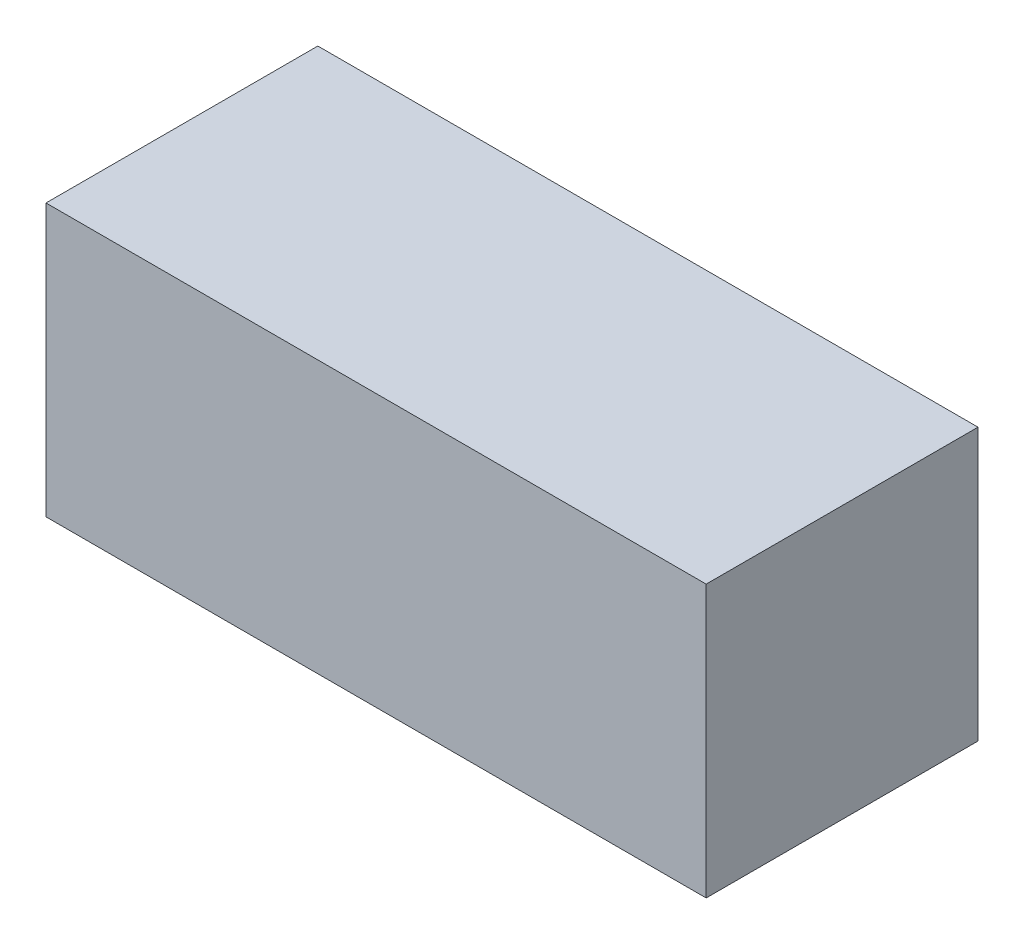
SolidWorks part; units mm, degrees
ref_plane "Front Plane"
ref_plane "Top Plane" through (0, 0, 0) normal (0, 1, 0) x (1, 0, 0)
ref_plane "Right Plane" through (0, 0, 0) normal (1, 0, 0) x (0, 0, -1)
sketch "Sketch1" plane through (0, 0, 0) normal (0, 1, 0) x (1, 0, 0)
  line L1 (-85, -35) -> (85, -35)
  line L2 (-85, -35) -> (-85, 35)
  line L3 (-85, 35) -> (85, 35)
  line L4 (85, -35) -> (85, 35)
  line L5 (-85, -35) -> (85, 35) construction
  line L6 (-85, 35) -> (85, -35) construction
  point P0 (0, 0)
  dimension "D1" = 170
  dimension "D2" = 70
extrude "Boss-Extrude1" add sketch "Sketch1" along normal blind 70
sketch "Sketch2" plane through (-85, 0, 0) normal (-1, 0, 0) x (0, 0, 1)
  line L0 (0, 0) -> (0, 70) construction
  line L4 (-35, 0) -> (35, 0)
  line L5 (35, 0) -> (35, 70)
  line L6 (35, 70) -> (-35, 70)
  line L7 (-35, 70) -> (-35, 0)
  line L8 (-35, 0) -> (35, 0) construction
  line L9 (35, 0) -> (35, 70) construction
  line L10 (35, 70) -> (-35, 70) construction
  line L11 (-35, 70) -> (-35, 0) construction
  point P6 (0, 35)
  point P7 (0, 0)
  point P8 (0, 17.4859)
  point P9 (0, 0)
  dimension "D1" = 0
ref_axis "Axis1" through (-79.0451, 35, 0) along (-1, 0, 0)
equation "\"TrackerMass\"= 100'judges tracker mass"
equation "\"CargoMass\"= 250'mass of cargo"
equation "\"X2814MotorDiameter\"= 35mm'Outer diameter of X2814 motor"
equation "\"X2814MotorLength\"= 36mm'X2814 Motor lenght"
equation "\"X2814PadHeight\"= 2mm"
equation "\"X2814ShaftDiameter\"= 4mm"
equation "\"X2814ShaftLength\"= 16mm"
equation "\"X2814PadDiameter\"= 11mm"
equation "\"X2814PadHoleCircleDiameter\"= 15mm"
equation "\"X2814PadScrewDiameter\"= 2.5mm"
equation "\"X2814WireLength\"= 110mm"
equation "\"X2814ShaftHoleLargeCircleDiameter\"= 25mm"
equation "\"X2814ShaftHoleSmallCircleDiameter\"= 19mm"
equation "\"X2814ShaftScrewDiameter\"= 3mm"
equation "\"X2814PadScrewDepth\"= 3.5mm"
equation "\"X2814ShaftScrewDepth\"= 3mm"
equation "\"X2814BaseOffset\"= 10mm"
